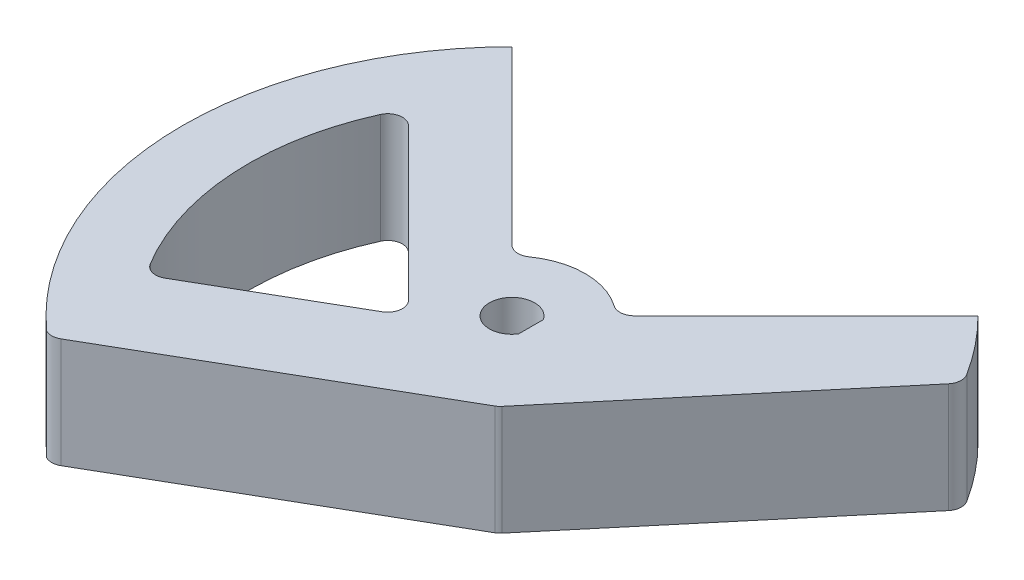
SolidWorks part; units mm, degrees
material "ABS"
ref_plane "Front Plane" through (0, 0, 0) normal (0, 0, 1) x (1, 0, 0)
ref_plane "Top Plane" through (0, 0, 0) normal (0, 1, 0) x (1, 0, 0)
ref_plane "Right Plane" through (0, 0, 0) normal (1, 0, 0) x (0, 0, -1)
sketch "Sketch1" plane through (0, 0, 0) normal (0, 1, 0) x (1, 0, 0)
  line L0 (-31.8198, 31.8198) -> (-7.0711, 7.0711)
  line L1 (7.0711, 7.0711) -> (31.8198, 31.8198)
  line L2 (0, 0) -> (0, 20) construction
  line L3 (0, 0) -> (-7.0711, 7.0711) construction
  line L4 (7.0711, 7.0711) -> (0, 0) construction
  arc A0 (-31.8198, 31.8198) -> (31.8198, 31.8198) centre (0, 0) ccw
  circle A1 centre (0, 0) radius 3
  arc A2 (7.0711, 7.0711) -> (-7.0711, 7.0711) centre (0, 0) ccw
  dimension "D1" = 6
  dimension "D2" = 90
  dimension "D3" = 20
  dimension "D4" = 45
extrude "Boss-Extrude1" add sketch "Sketch1" along normal blind 15
sketch "Sketch2" plane through (0, 15, 0) normal (0, 1, 0) x (1, 0, 0)
  line L0 (2.5, 1.6583) -> (2.5, -1.6583)
  line L1 (-3, 0) -> (-3, -6.6376) construction
  arc A0 (2.5, -1.6583) -> (2.5, 1.6583) centre (0, 0) ccw
  circle A1 centre (0, 0) radius 3 construction
  dimension "D1" = 5.5
extrude "Shaft D" add sketch "Sketch2" against normal up to surface (15 mm away) up to face at (0, 0, -0.9727)
sketch "Sketch3" plane through (0, 15, 0) normal (0, 1, 0) x (1, 0, 0)
  line L0 (-31.8198, 31.8198) -> (-27.5772, 36.0624)
  line L1 (-27.5772, 36.0624) -> (-27.5772, 27.5772)
  line L2 (-7.0711, 7.0711) -> (-31.8198, 31.8198) construction
  line L3 (-27.5772, 27.5772) -> (-31.8198, 31.8198)
  line L4 (0, 0) -> (0, 30.6174) construction
  line L5 (27.5772, 27.5772) -> (31.8198, 31.8198)
  line L6 (27.5772, 36.0624) -> (27.5772, 27.5772)
  line L7 (31.8198, 31.8198) -> (27.5772, 36.0624)
  dimension "D1" = 6
extrude "Boss-Extrude2" [suppressed] add sketch "Sketch3" against normal up to surface (15 mm away)
sketch "Sketch5" plane through (0, 15, 0) normal (0, 1, 0) x (1, 0, 0)
  line L0 (31.8198, 31.8198) -> (0, 0) construction
  line L1 (0, 0) -> (-31.8198, 31.8198) construction
  line L2 (-31.8198, 31.8198) -> (31.8198, 31.8198) construction
sketch "Sketch4" plane through (0, 15, 0) normal (0, 1, 0) x (1, 0, 0)
  line L0 (-148.943, 0) -> (142.5774, 0) construction
  line L1 (0, 0) -> (-107.5774, -62.1099) construction
  line L2 (0, 0) -> (96.6052, -81.0614) construction
  line L8 (0, 0) -> (81.0614, 96.6052) construction
  line L9 (0, 0) -> (62.1099, -107.5774) construction
  line L10 (-107.5774, -62.1099) -> (62.1099, -107.5774) construction
  line L11 (81.0614, 96.6052) -> (96.6052, -81.0614) construction
  line L14 (11.4907, -9.6418) -> (45.5038, 30.8934)
  line L15 (11.4907, -9.6418) -> (-38.9929, -38.7885)
  arc A2 (-38.9929, -38.7885) -> (45.5038, 30.8934) centre (0, 0) ccw
  dimension "D4" = 55
  dimension "D1" = 40
  dimension "D3" = 30
  dimension "D5" = 15
extrude "Cut-Extrude1" cut sketch "Sketch4" against normal through all
sketch "Sketch6" plane through (7.0477, 0, 12.207) normal (0.5, 0, 0.866) x (0.866, 0, -0.5)
  line L0 (5.1303, 0) -> (-42.7355, 0) construction
  line L1 (-42.7355, 15) -> (5.1303, 15)
  line L2 (-42.7355, 15) -> (-42.7355, 0)
  line L3 (-42.7355, 0) -> (5.1303, 0)
  line L4 (5.1303, 15) -> (5.1303, 0)
  line L5 (-42.7355, 15) -> (5.1303, 0) construction
  line L6 (-42.7355, 0) -> (5.1303, 15) construction
  point P4 (-18.8026, 7.5)
extrude "Boss-Extrude3" add sketch "Sketch6" along normal blind 0.9
sketch "Sketch7" plane through (0, 15, 0) normal (0, 1, 0) x (1, 0, 0)
  line L0 (-31.5251, 17.383) -> (-7.0711, -7.0711)
  line L1 (-7.0711, -7.0711) -> (-29.8021, -20.1949)
  line L2 (11.9407, -10.4212) -> (-29.5123, -34.3541) construction
  line L3 (-7.0711, 7.0711) -> (-31.8198, 31.8198) construction
  arc A0 (-31.5251, 17.383) -> (-29.8021, -20.1949) centre (0, 0) ccw
  dimension "D1" = 36
  dimension "D3" = 10
  dimension "D4" = 12.4072
extrude "Cut-Extrude2" cut sketch "Sketch7" against normal through all contours L0 L1 A0
sketch "Sketch9" plane through (0, 15, 0) normal (0, 1, 0) x (1, 0, 0)
  line L0 (2.5, 1.6583) -> (2.5, -1.6583) construction
  line L1 (2.59, 1.6852) -> (2.59, -1.6852)
  arc A0 (2.5, 1.6583) -> (2.5, -1.6583) centre (0, 0) ccw construction
  arc A1 (2.59, 1.6852) -> (2.59, -1.6852) centre (0, 0) ccw
  dimension "D1" = 0.09
extrude "Shaft Hole Expansion" cut sketch "Sketch9" against normal through all
sketch "Sketch10" plane through (0, 15, 0) normal (0, 1, 0) x (1, 0, 0)
  line L0 (11.4907, -9.6418) -> (7.4934, -14.4056)
  line L1 (7.4934, -14.4056) -> (21.6668, -15.2895)
  line L2 (21.6668, -15.2895) -> (11.4907, -9.6418)
  line L3 (38.7618, 22.8587) -> (11.4907, -9.6418) construction
  line L4 (11.4907, -9.6418) -> (13.8307, -6.8531) construction
extrude "Cut-Extrude4" cut sketch "Sketch10" against normal through all
fillet "Fillet1" radius 2 8 edges at (-29.8021, 7.5, 20.1949) (-31.5251, 7.5, -17.383) (-7.0711, 7.5, 7.0711) (-7.0711, 7.5, -7.0711) (7.0711, 7.5, -7.0711) (-29.5123, 7.5, 34.3541) (9.7992, 7.5, 11.6576) (38.7618, 7.5, -22.8587)
